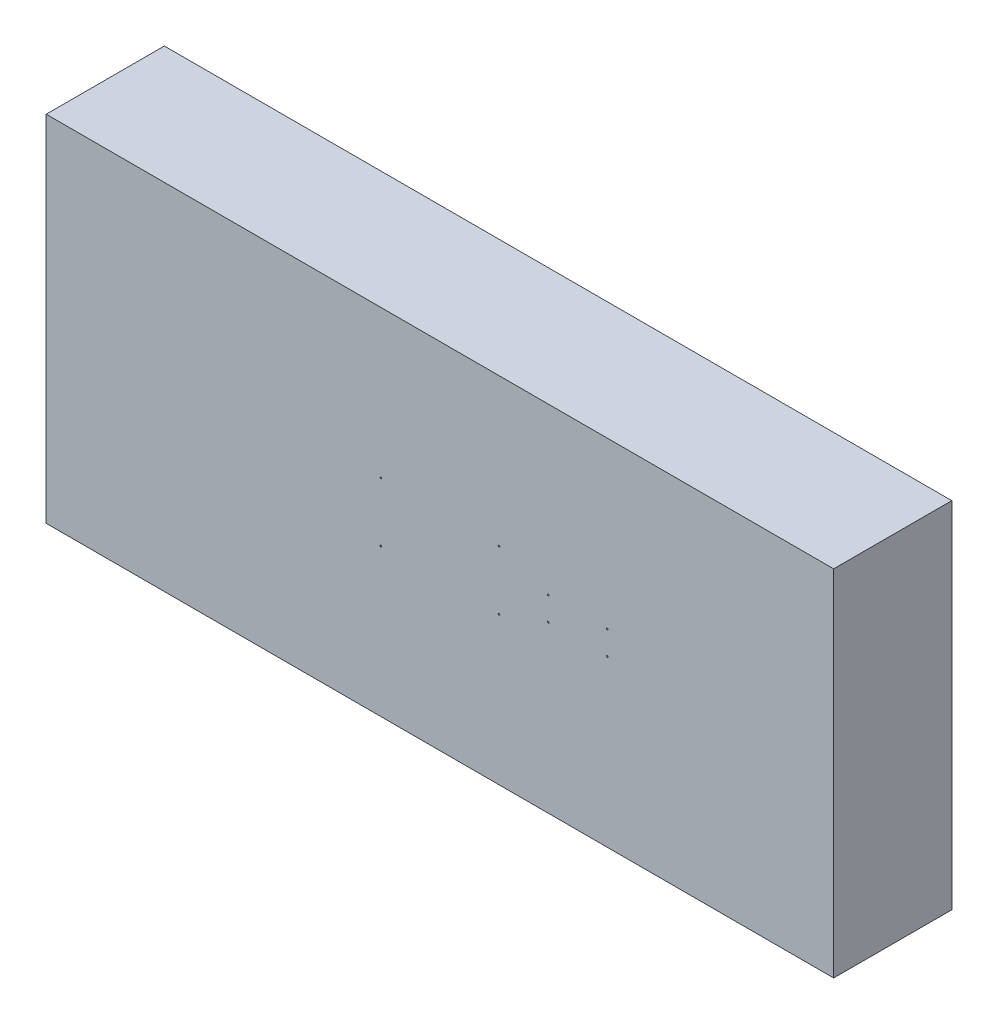
SolidWorks part; units mm, degrees
material "Cast Alloy Steel"
ref_plane "Front Plane" through (0, 0, 0) normal (1, 0, 0) x (0, 1, 0)
ref_plane "Top Plane" through (0, 0, 0) normal (0, 0, 1) x (0, 1, 0)
ref_plane "Right Plane" through (0, 0, 0) normal (0, 1, 0) x (-1, 0, 0)
sketch "Sketch1" plane through (0, 0, 0) normal (1, 0, 0) x (0, 1, 0)
  line L1 (0, -55) -> (0, 55) construction
  line L2 (-450, 150) -> (0, 150)
  line L3 (-450, 150) -> (-450, 0)
  line L4 (-450, 0) -> (0, 0)
  line L5 (0, 150) -> (0, 0)
  line L6 (0, 150) -> (150, 150)
  line L7 (0, 150) -> (0, 1150)
  line L8 (0, 1150) -> (150, 1150)
  line L9 (150, 150) -> (150, 1150)
  line L10 (-450, 0) -> (-600, 0)
  line L11 (-450, 0) -> (-450, -500)
  line L12 (-450, -500) -> (-600, -500)
  line L13 (-600, 0) -> (-600, -500)
  line L14 (55, 0) -> (-55, 0) construction
  dimension "D1" = 1000
  dimension "D2" = 150
  dimension "D3" = 150
  dimension "D4" = 150
  dimension "D5" = 450
  dimension "D6" = 500
  dimension "D7" = 0
  dimension "D8" = 0
extrude "Boss-Extrude2" add sketch "Sketch1" along normal blind 500 and the other way blind 500 contours L5 L2 L3 L4 region at (0, -225, 75)
sketch "Sketch2" plane through (0, 0, 150) normal (0, 0, 1) x (1, 0, 0)
  line L1 (-75, -187.5) -> (75, -187.5)
  line L2 (-75, -187.5) -> (-75, -262.5)
  line L3 (-75, -262.5) -> (75, -262.5)
  line L4 (-500, -450) -> (500, -450)
  line L5 (500, -450) -> (500, 0)
  line L6 (500, 0) -> (-500, 0)
  line L7 (-500, 0) -> (-500, -450)
  line L8 (-500, -450) -> (500, -450)
  line L9 (500, -450) -> (500, 0)
  line L10 (500, 0) -> (-500, 0)
  line L11 (-500, 0) -> (-500, -450)
  line L12 (75, -187.5) -> (75, -262.5)
  point P8 (0, -187.5)
  point P10 (-75, -225)
  point P11 (-500, -225)
  point P13 (-75, -187.5)
  point P14 (-75, -262.5)
  point P15 (75, -187.5)
  point P16 (75, -262.5)
  dimension "D2" = 0
  dimension "D3" = 0
  dimension "D4" = 75
  dimension "D5" = 150
  dimension "D1" = 0
hole_wizard "Ø2.0mm Dowel Hole1" positions "Sketch2" profile "Sketch3" hole size "Ø2.0" standard "IS"
sketch "Sketch3" plane through (75, -262.5, 150) normal (1, 0, 0) x (0, -1, 0)
  line L0 (0, 0) -> (0, 10.6009)
  line L1 (0, 10.6009) -> (1, 10)
  line L2 (1, 10) -> (1, 0.025)
  line L3 (1, 0.025) -> (1.025, 0)
  line L5 (1.025, 0) -> (0, 0)
  line L6 (-1, 0.025) -> (-1.025, 0) construction
  line L10 (0, 10.6009) -> (-1, 10) construction
  line L11 (0, -6.35) -> (0, 107.95) construction
  dimension "Hole Dia." = 2
  dimension "Hole Depth" = 10
  dimension "Near C'Sink Dia." = 2.05
  dimension "Near C'Sink Angle" = 90
  dimension "Drill Angle" = 118
sketch "Sketch4" plane through (0, 0, 150) normal (0, 0, 1) x (1, 0, 0)
  line L1 (137.5, -210) -> (212.5, -210)
  line L2 (137.5, -210) -> (137.5, -240)
  line L3 (137.5, -240) -> (212.5, -240)
  line L4 (212.5, -210) -> (212.5, -240)
  line L8 (-500, -450) -> (500, -450)
  line L9 (500, -450) -> (500, 0)
  line L10 (500, 0) -> (-500, 0)
  line L11 (-500, 0) -> (-500, -450)
  line L12 (-500, -450) -> (500, -450)
  line L13 (500, -450) -> (500, 0)
  line L14 (500, 0) -> (-500, 0)
  line L15 (-500, 0) -> (-500, -450)
  point P6 (-500, -225)
  point P8 (137.5, -225)
  point P11 (137.5, -210)
  point P13 (137.5, -240)
  point P14 (212.5, -240)
  point P15 (212.5, -210)
  point P89 (175, -210)
  dimension "D2" = 0
  dimension "D3" = 75
  dimension "D4" = 30
  dimension "D5" = 175
  dimension "D1" = 0
hole_wizard "Ø2.0mm Dowel Hole2" positions "Sketch4" profile "Sketch5" hole size "Ø2.0" standard "IS"
sketch "Sketch5" plane through (212.5, -210, 150) normal (1, 0, 0) x (0, -1, 0)
  line L0 (0, 0) -> (0, 10.6009)
  line L1 (0, 10.6009) -> (1, 10)
  line L2 (1, 10) -> (1, 0.025)
  line L3 (1, 0.025) -> (1.025, 0)
  line L5 (1.025, 0) -> (0, 0)
  line L6 (-1, 0.025) -> (-1.025, 0) construction
  line L10 (0, 10.6009) -> (-1, 10) construction
  line L11 (0, -6.35) -> (0, 107.95) construction
  dimension "Hole Dia." = 2
  dimension "Hole Depth" = 10
  dimension "Near C'Sink Dia." = 2.05
  dimension "Near C'Sink Angle" = 90
  dimension "Drill Angle" = 118
